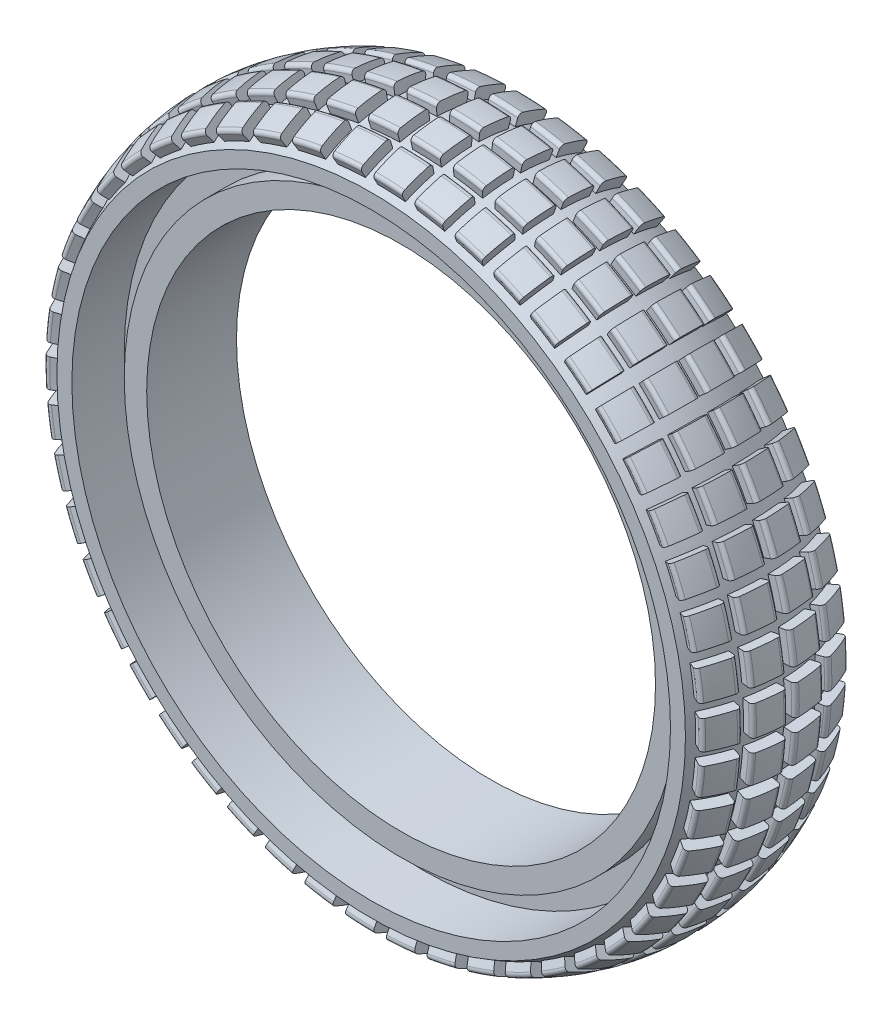
SolidWorks part; units mm, degrees
material "Cast Alloy Steel"
ref_plane "Front Plane" through (0, 0, 0) normal (0, 0, 1) x (1, 0, 0)
ref_plane "Top Plane" through (0, 0, 0) normal (0, 1, 0) x (1, 0, 0)
ref_plane "Right Plane" through (0, 0, 0) normal (1, 0, 0) x (0, 0, -1)
sketch "Sketch1" plane through (0, 0, 0) normal (1, 0, 0) x (0, 0, -1)
  line L0 (0, 0) -> (0, 1.5)
  line L1 (0, 1.5) -> (1.5, 1.5)
  line L2 (1.5, 1.5) -> (1.5, 3)
  line L4 (-2, 3) -> (-2, 4)
  line L5 (0, 0) -> (6, 0)
  line L6 (3, 0) -> (3, 6.9228) construction
  line L7 (8, 3) -> (8, 4)
  line L9 (4.5, 1.5) -> (4.5, 3)
  line L10 (6, 1.5) -> (4.5, 1.5)
  line L11 (6, 0) -> (6, 1.5)
  line L12 (6, 0) -> (6, -17) construction
  line L13 (6, -17) -> (-4, -17) construction
  line L14 (-2, 3) -> (1.5, 3)
  line L15 (4.5, 3) -> (8, 3)
  arc A2 (-2, 4) -> (8, 4) centre (3, -4.5446) cw
  dimension "D5" = 9.9
  dimension "D1" = 1.5
  dimension "D2" = 1.5
  dimension "D3" = 1
  dimension "D4" = 3
  dimension "D7" = 17
  dimension "D8" = 3.5
revolve "Revolve1" add sketch "Sketch1" angle 360 about L13
ref_axis "Axis1" through (0, -17, 0) along (0, 0, -1)
sketch "Sketch2" plane through (0, 0, 0) normal (1, 0, 0) x (0, 0, -1)
  line L0 (-2, 4) -> (-2.3787, 4.6473) construction
  line L1 (-2, 4) -> (3, -4.5462) construction
  line L2 (0.7736, 5.1016) -> (0.6618, 5.5859)
  line L3 (5.2264, 5.1016) -> (5.3382, 5.5859)
  line L4 (3, 5.3552) -> (3, 6.1052) construction
  line L5 (3, -4.5462) -> (-1.5622, 4.2415) construction
  line L6 (3, -4.5462) -> (0.2894, 4.9769) construction
  line L7 (3.25, 5.352) -> (3.25, 5.8432)
  line L8 (3, -4.5462) -> (2.75, 5.352) construction
  line L9 (-1.5622, 4.2415) -> (0.2894, 4.9769) construction
  line L10 (7.5622, 4.2415) -> (7.7912, 4.6826)
  line L11 (0.7736, 5.1016) -> (2.75, 5.352) construction
  line L12 (-1.5622, 4.2415) -> (-1.7912, 4.6826)
  line L13 (4.4731, -10.9295) -> (3, -4.5462)
  line L14 (0.1641, 5.453) -> (0.2894, 4.9769)
  line L15 (5.8359, 5.453) -> (5.7106, 4.9769)
  line L16 (2.75, 5.352) -> (2.75, 5.8432)
  arc A0 (0.855, 5.887) -> (2.488, 6.0929) centre (3, -4.5462) cw
  arc A1 (-1.5622, 4.2415) -> (0.2894, 4.9769) centre (3, -4.5462) cw
  arc A2 (-1.6791, 5.0224) -> (-0.1516, 5.6282) centre (3, -4.5462) cw
  arc A3 (0.7736, 5.1016) -> (2.75, 5.352) centre (3, -4.5462) cw
  arc A4 (5.2264, 5.1016) -> (3.25, 5.352) centre (3, -4.5462) ccw
  arc A5 (5.145, 5.887) -> (3.512, 6.0929) centre (3, -4.5462) ccw
  arc A6 (7.6791, 5.0224) -> (6.1516, 5.6282) centre (3, -4.5462) ccw
  arc A7 (7.5622, 4.2415) -> (5.7106, 4.9769) centre (3, -4.5462) ccw
  arc A8 (-0.1516, 5.6282) -> (0.1641, 5.453) centre (-0.0777, 5.3894) cw
  arc A9 (2.75, 5.8432) -> (2.488, 6.0929) centre (2.5, 5.8432) ccw
  arc A10 (3.25, 5.8432) -> (3.512, 6.0929) centre (3.5, 5.8432) cw
  arc A11 (6.1516, 5.6282) -> (5.8359, 5.453) centre (6.0777, 5.3894) ccw
  arc A12 (5.3382, 5.5859) -> (5.145, 5.887) centre (5.0946, 5.6421) ccw
  arc A13 (0.6618, 5.5859) -> (0.855, 5.887) centre (0.9054, 5.6421) cw
  arc A14 (-1.7912, 4.6826) -> (-1.6791, 5.0224) centre (-1.5693, 4.7978) cw
  arc A15 (7.6791, 5.0224) -> (7.7912, 4.6826) centre (7.5693, 4.7978) cw
  point P26 (0.0985, 5.7024)
  point P29 (2.75, 6.1023)
  point P32 (3.25, 6.1023)
  point P35 (5.9015, 5.7024)
  point P38 (5.3951, 5.8324)
  point P41 (0.6049, 5.8324)
  point P44 (-1.9078, 4.9072)
  point P47 (7.9078, 4.9072)
  dimension "D5" = 0.25
  dimension "D1" = 0.75
  dimension "D2" = 0.5
  dimension "D3" = 0.5
  dimension "D4" = 0.25
revolve "Revolve2" add sketch "Sketch2" angle 5 about axis through (0, -17, 0) along (0, 0, -1) region at (0, 5.6317, -1.7147) region at (0, 5.6317, -4.2853) region at (0, 4.9892, -6.7837) region at (0, 4.9892, 0.7837)
pattern_circular "CirPattern1" count 50 over 360 about axis through (0, -17, 0) along (0, 0, -1) of "Revolve2"
